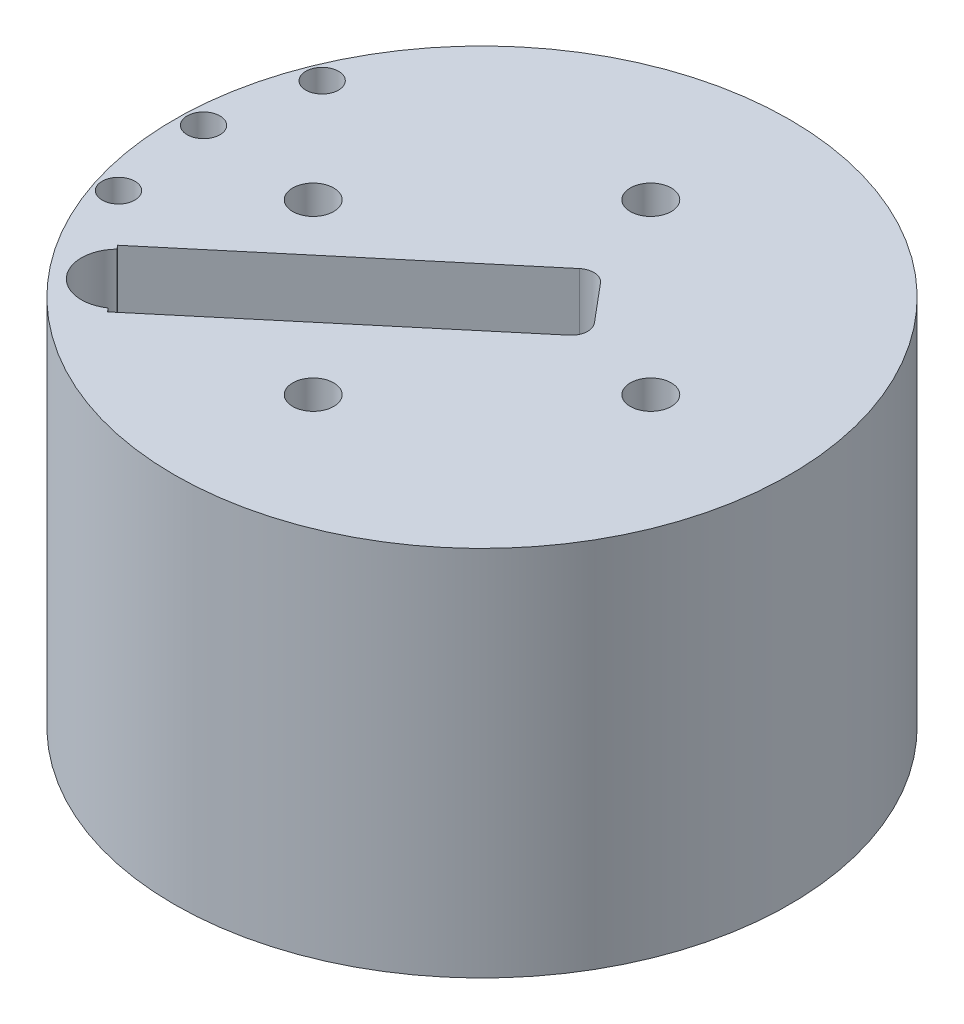
SolidWorks part; units mm, degrees
ref_plane "Front Plane" through (0, 0, 0) normal (0, 0, 1) x (1, 0, 0)
ref_plane "Top Plane" through (0, 0, 0) normal (0, 1, 0) x (1, 0, 0)
ref_plane "Right Plane" through (0, 0, 0) normal (1, 0, 0) x (0, 0, -1)
sketch "Sketch2" plane through (0, 0, 0) normal (0, 1, 0) x (1, 0, 0)
  circle A0 centre (0, 0) radius 47.6885
  dimension "D1" = 95.377
extrude "Boss-Extrude1" add sketch "Sketch2" along normal blind 57.658
sketch "Sketch4" plane through (0, 57.658, 0) normal (0, 1, 0) x (1, 0, 0)
  circle A1 centre (-26.162, 0) radius 3.175
  circle A2 centre (26.162, 0) radius 3.175
  circle A3 centre (0, 26.162) radius 3.175
  circle A4 centre (0, -26.162) radius 3.175
sketch "Sketch5" plane through (0, 57.658, 0) normal (0, 1, 0) x (1, 0, 0)
  line L0 (0, 0) -> (-44.6487, 1.4926)
  line L1 (0, 0) -> (-41.4455, 16.6734)
  line L2 (0, 0) -> (-42.4665, -13.8681)
  line L4 (0, 0) -> (-30.6943, -25.7555)
  circle A1 centre (-41.4455, 16.6734) radius 2.54
  circle A2 centre (0, 0) radius 44.6736
  circle A3 centre (-44.6487, 1.4926) radius 2.54
  circle A4 centre (-42.4665, -13.8681) radius 2.54
  circle A9 centre (-30.6943, -25.7555) radius 5.6388
  dimension "D3" = 11.2776
  dimension "D5" = 89.3472
  dimension "D1" = 20
  dimension "D2" = 20
  dimension "D6" = 21.915
  dimension "D4" = 40.0685
extrude "Cut-Extrude2" cut sketch "Sketch5" against normal through all contours A9 | A1 | A3 | A4
extrude "Cut-Extrude3" cut sketch "Sketch4" against normal through all
sketch "Sketch6" plane through (0, 57.658, 0) normal (0, 1, 0) x (1, 0, 0)
  line L1 (-27.0503, -30.9873) -> (13.8105, 3.299)
  line L2 (-27.0503, -30.9873) -> (-35.2137, -21.2585)
  line L3 (-35.2137, -21.2585) -> (5.6471, 13.0278)
  line L4 (13.8105, 3.299) -> (5.6471, 13.0278)
  dimension "D1" = 53.34
  dimension "D2" = 12.7
  dimension "D3" = 6.35
  dimension "D4" = 12.7
  dimension "D5" = 90
  dimension "D6" = 90
  dimension "D7" = 90
extrude "Cut-Extrude4" cut sketch "Sketch6" against normal blind 25.4
fillet "Fillet2" radius 2.54 5 edges at (-6.6199, 32.258, 13.8441) (-14.7833, 32.258, 4.1154) (9.7288, 32.258, -8.1634) (13.8105, 44.958, -3.299) (5.6471, 44.958, -13.0278)
fillet "Fillet3" radius 2.54 3 edges at (-25.6003, 32.626, 28.1738) (-33.0634, 32.8522, 20.6386) (-26.3747, 32.258, 22.131)
sketch "Sketch11" plane through (0, 0, 0) normal (0, -1, 0) x (1, 0, 0)
  circle A0 centre (0, 26.162) radius 6.35
  circle A1 centre (26.162, 0) radius 6.35
  circle A2 centre (0, -26.162) radius 6.35
  circle A3 centre (-26.162, 0) radius 6.35
  dimension "D1" = 12.7
  dimension "D2" = 12.7
  dimension "D3" = 12.7
  dimension "D4" = 12.7
extrude "Cut-Extrude7" cut sketch "Sketch11" against normal blind 7.62
sketch "Sketch14" plane through (0, 0, 0) normal (0, -1, 0) x (1, 0, 0)
  circle A0 centre (1.3569, -14.949) radius 2.067
  circle A1 centre (4.5237, 8.9723) radius 2.067
extrude "Cut-Extrude8" cut sketch "Sketch14" against normal blind 19.05
equation "\"D4@Sketch5\"=(3.755/2)-(0.5/2)-0.05"
